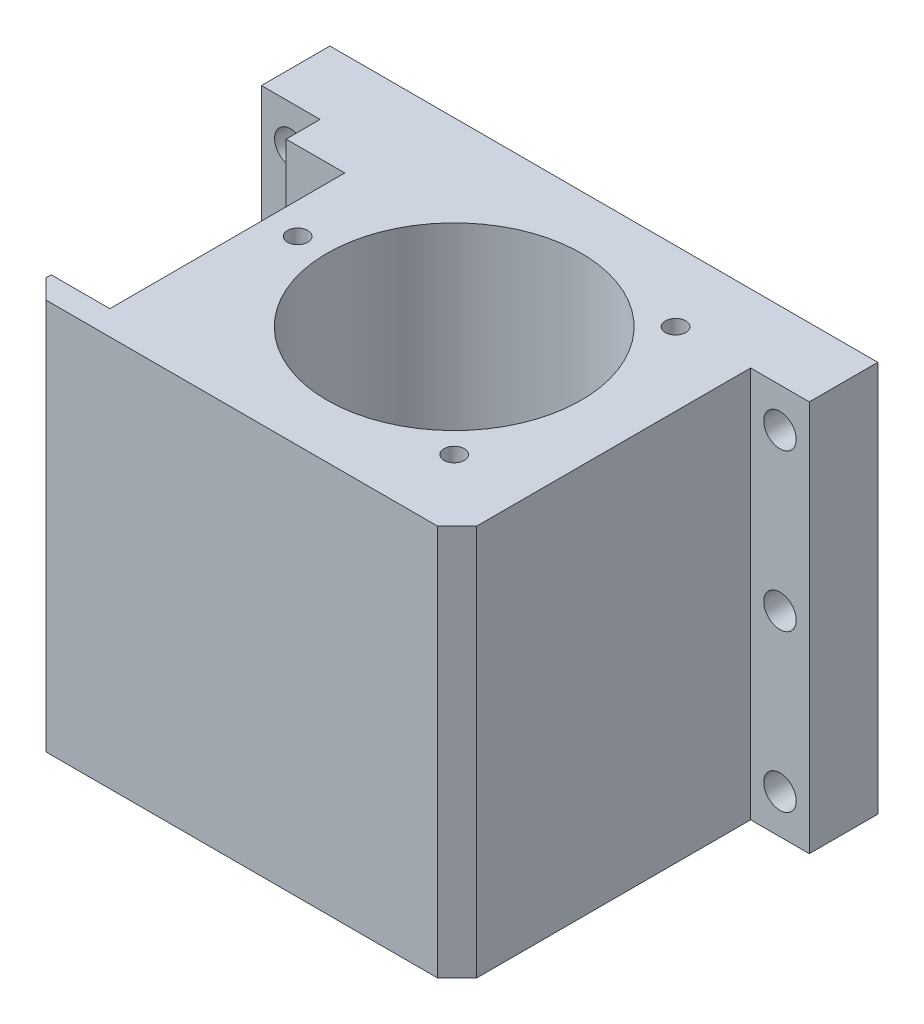
SolidWorks part; units mm, degrees
material "3.3315 (EN-AW 5005)"
ref_plane "前视基准面" through (0, 0, 0) normal (0, 0, 1) x (1, 0, 0)
ref_plane "上视基准面" through (0, 0, 0) normal (0, 1, 0) x (1, 0, 0)
ref_plane "右视基准面" through (0, 0, 0) normal (1, 0, 0) x (0, 0, -1)
other "Configuration Table"
sketch "草图1" plane through (0, 0, 0) normal (0, 0, 1) x (1, 0, 0)
  line L1 (0, 0) -> (140, 0)
  line L2 (0, 0) -> (0, -100)
  line L3 (0, -100) -> (140, -100)
  line L4 (140, 0) -> (140, -100)
  dimension "D1" = 140
  dimension "D2" = 100
extrude "凸台-拉伸1" add sketch "草图1" along normal blind 92.5
sketch "草图2" plane through (0, 0, 0) normal (0, 1, 0) x (1, 0, 0)
  line L0 (140, -46.25) -> (0, -46.25) construction
  line L1 (140, -92.5) -> (140, 0) construction
  line L2 (0, -92.5) -> (0, 0) construction
  circle A0 centre (78, -46.25) radius 32.51
  dimension "D1" = 65.02
  dimension "D2" = 62
extrude "切除-拉伸1" cut sketch "草图2" against normal through all
sketch "草图3" plane through (0, 0, 92.5) normal (0, 0, 1) x (1, 0, 0)
  line L0 (70, 0) -> (70, -100) construction
  line L1 (140, 0) -> (0, 0) construction
  line L2 (0, -100) -> (140, -100) construction
  line L3 (0, 0) -> (0, -100) construction
  line L4 (15, 0) -> (125, 0)
  line L5 (15, 0) -> (15, -100)
  line L6 (15, -100) -> (125, -100)
  line L7 (125, 0) -> (125, -100)
  dimension "D1" = 110
  dimension "D2" = 15
extrude "切除-拉伸2" cut sketch "草图3" against normal blind 75 flip side to cut
sketch "草图4" plane through (0, 0, 0) normal (0, 1, 0) x (1, 0, 0)
  circle A0 centre (78, -46.25) radius 46 construction
  dimension "D1" = 92
sketch "草图5" plane through (15, 0, 0) normal (-1, 0, 0) x (0, 0, 1)
  line L0 (46.25, 0) -> (46.25, -100) construction
  line L1 (92.25, 0) -> (0.25, 0) construction
  line L2 (17.5, -100) -> (92.5, -100) construction
  line L4 (26.2, 0) -> (86.25, 0)
  line L5 (26.2, 0) -> (26.2, -100)
  line L6 (26.2, -100) -> (86.25, -100)
  line L7 (86.25, 0) -> (86.25, -100)
  dimension "D1" = 60.05
  dimension "D2" = 40
extrude "切除-拉伸3" cut sketch "草图5" against normal blind 15
chamfer "倒角2" distance 5 angle 45 2 edges at (125, -50, 92.5) (15, -50, 92.5)
sketch "草图6" plane through (0, -100, 0) normal (0, -1, 0) x (1, 0, 0)
  line L0 (78, 46.25) -> (78, 92.25) construction
  circle A0 centre (78, 46.25) radius 39.5 construction
  circle A1 centre (78, 46.25) radius 46 construction
  circle A2 centre (78, 85.75) radius 2.6
  circle A3 centre (112.208, 66) radius 2.6
  circle A4 centre (112.208, 26.5) radius 2.6
  circle A5 centre (78, 6.75) radius 2.6
  circle A6 centre (43.792, 26.5) radius 2.6
  circle A7 centre (43.792, 66) radius 2.6
  point P20 (78, 46.25)
  dimension "D1" = 79
  dimension "D2" = 5.2
  dimension "D3" = 6
extrude "切除-拉伸4" cut sketch "草图6" against normal blind 20
sketch "草图9" plane through (0, 0, 17.5) normal (0, 0, 1) x (1, 0, 0)
  line L0 (0, 0) -> (0, -100) construction
  line L1 (15, 0) -> (0, 0) construction
  circle A0 centre (7.5, -10) radius 4.15
  circle A1 centre (132.5, -10) radius 4.15
  circle A2 centre (132.5, -50) radius 4.15
  circle A3 centre (132.5, -90) radius 4.15
  circle A4 centre (7.5, -50) radius 4.15
  circle A5 centre (7.5, -90) radius 4.15
  dimension "D1" = 8.3
  dimension "D4" = 2
  dimension "D2" = 7.5
  dimension "D3" = 10
  dimension "D5" = 3
extrude "切除-拉伸5" cut sketch "草图9" against normal through all
sketch "草图10" plane through (0, 0, 0) normal (0, 1, 0) x (1, 0, 0)
  line L0 (38, -46.25) -> (118, -46.25) construction
  line L1 (78, -46.25) -> (78, -6.25) construction
  line L2 (78, -46.25) -> (49.7157, -17.9657) construction
  circle A0 centre (78, -46.25) radius 40 construction
  circle A3 centre (106.2843, -17.9657) radius 2.6
  circle A4 centre (106.2843, -74.5343) radius 2.6
  circle A6 centre (38, -46.25) radius 2.6
  point P18 (78, -46.25)
  dimension "D1" = 80
  dimension "D4" = 5.2
extrude "切除-拉伸6" cut sketch "草图10" against normal blind 20
